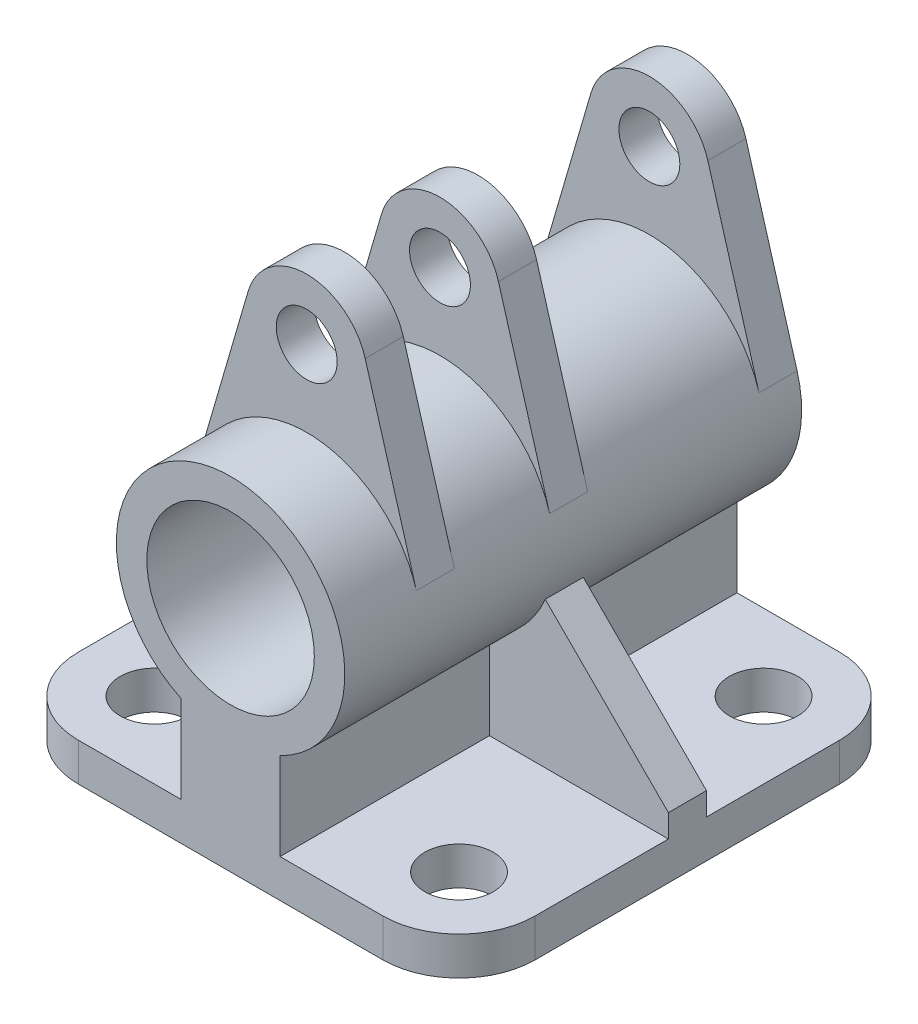
SolidWorks part; units mm, degrees
ref_plane "Спереди" through (0, 0, 0) normal (0, 0, 1) x (1, 0, 0)
ref_plane "Сверху" through (0, 0, 0) normal (0, 1, 0) x (1, 0, 0)
ref_plane "Справа" through (0, 0, 0) normal (1, 0, 0) x (0, 0, -1)
sketch "Эскиз2" plane through (0, 0, 0) normal (0, 0, 1) x (1, 0, 0)
  line L0 (0, 28.7468) -> (0, -28.7468) construction
  line L1 (6.5, -13.5185) -> (6.5, -25)
  line L2 (6.5, -25) -> (30, -25)
  line L3 (13.8234, -5.8234) -> (30, -22)
  line L4 (30, -22) -> (30, -30)
  line L5 (30, -30) -> (-30, -30)
  line L6 (7.68, 27.24) -> (14.4, 4.2)
  line L9 (-30, -22) -> (-30, -30)
  line L10 (-6.5, -25) -> (-30, -25)
  line L11 (-6.5, -13.5185) -> (-6.5, -25)
  line L12 (-13.8234, -5.8234) -> (-30, -22)
  line L13 (-7.68, 27.24) -> (-14.4, 4.2)
  circle A0 centre (0, 0) radius 11
  circle A1 centre (0, 0) radius 15
  circle A2 centre (0, 25) radius 4
  arc A3 (7.68, 27.24) -> (-7.68, 27.24) centre (0, 25) ccw
  point P7 (0, 0)
  point P20 (0, -30)
  dimension "D1" = 22
  dimension "D2" = 30
  dimension "D9" = 8
  dimension "D11" = 63
  dimension "D3" = 8
  dimension "D4" = 45
  dimension "D5" = 5
  dimension "D6" = 13
  dimension "D7" = 60
  dimension "D8" = 30
  dimension "D10" = 55
extrude "Бобышка-Вытянуть2" add sketch "Эскиз2" along normal mid plane 60 contours A1 L0 L5 L4 L2 L1 | L0 A1 L11 L10 L9 L5 | L0 A1 A0 | A1 L0 A0 region at (8.7988, 11.7317, 0) region at (-0.3354, 13, 0) region at (3.4716, -15.2316, 0)
extrude "Бобышка-Вытянуть3" add sketch "Эскиз2<6>" along normal mid plane 5 contours L0 A3 L13 A1 A2 | A3 L0 A2 A1 L6 | A1 L1 L2 L4 L3 | A1 L12 L9 L10 L11 region at (-9.2444, 12.3258, 0) region at (-16.4394, -18.1684, 0) region at (16.4394, -18.1684, 0)
sketch "Эскиз2<6>" plane through (0, 0, 0) normal (0, 0, 1) x (1, 0, 0) same geometry as "Эскиз2"
extrude "Бобышка-Вытянуть4" add sketch "Эскиз2<8>" along normal blind 5 from offset 15 contours A3 L0 A2 A1 L6 | L0 A3 L13 A1 A2 region at (-9.2444, 12.3258, 0)
sketch "Эскиз2<8>" plane through (0, 0, 0) normal (0, 0, 1) x (1, 0, 0) same geometry as "Эскиз2"
extrude "Бобышка-Вытянуть5" add sketch "Эскиз2<9>" along normal blind 5 from vertex contours A3 L0 A2 A1 L6 | L0 A3 L13 A1 A2 region at (-9.2444, 12.3258, 0) starting at point (6.5, -13.5185, -30)
sketch "Эскиз2<9>" plane through (0, 0, 0) normal (0, 0, 1) x (1, 0, 0) same geometry as "Эскиз2"
sketch "Эскиз4" plane through (0, -25, 0) normal (0, 1, 0) x (1, 0, 0)
  line L0 (0, 0) -> (0, 18.3469) construction
  line L1 (0, 0) -> (20, 0) construction
  circle A0 centre (20, 20) radius 4.5
  dimension "D1" = 9
  dimension "D2" = 20
  dimension "D3" = 20
extrude "Вырез-Вытянуть1" cut sketch "Эскиз4" against normal through all
mirror "Зеркальное отражение1" about plane through (0, 0, 0) normal (0, 0, 1) of "Вырез-Вытянуть1"
mirror "Зеркальное отражение2" about plane through (0, 0, 0) normal (1, 0, 0) of "Зеркальное отражение1"
fillet "Скругление1" radius 10 4 edges at (30, -27.5, -30) (30, -27.5, 30) (-30, -27.5, 30) (-30, -27.5, -30)
equation "\"D3@Эскиз4\"=\"D2@Эскиз4\""
